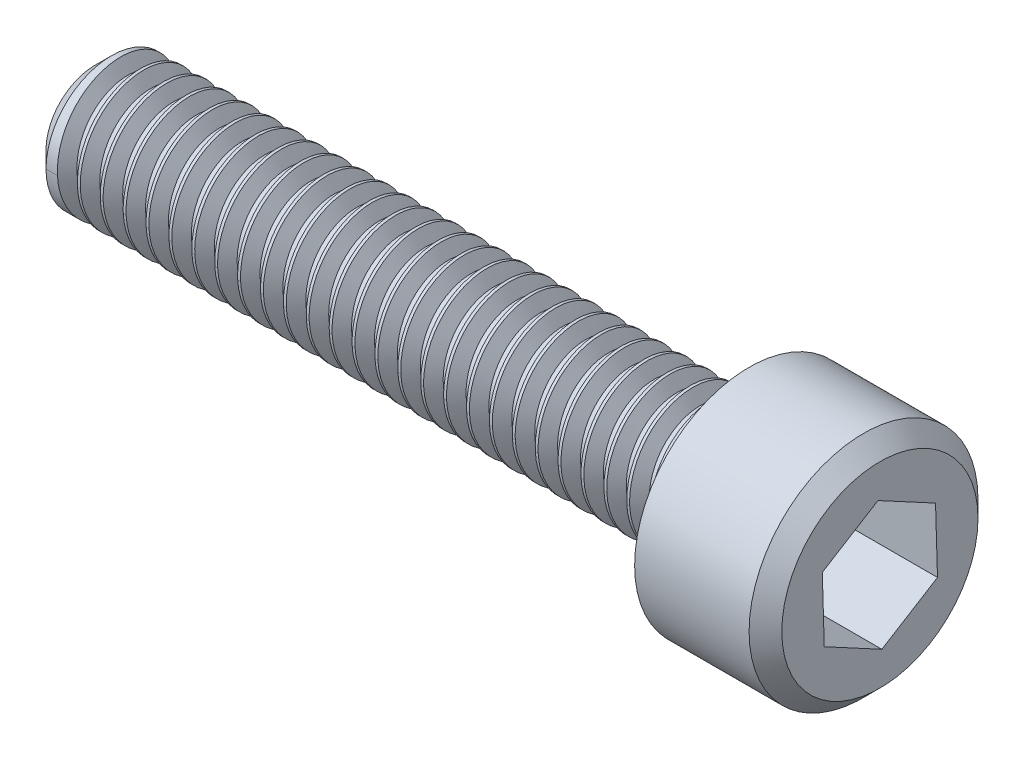
SolidWorks part; units mm, degrees
material "Хромистая нержавеющая сталь"
ref_plane "Спереди" through (0, 0, 0) normal (0, 0, 1) x (1, 0, 0)
ref_plane "Сверху" through (0, 0, 0) normal (0, 1, 0) x (1, 0, 0)
ref_plane "Справа" through (0, 0, 0) normal (1, 0, 0) x (0, 0, -1)
sketch "Эскиз1" plane through (0, 0, 0) normal (0, 0, 1) x (1, 0, 0)
  line L0 (-18.4706, 0) -> (28.3529, 0) construction
  line L1 (18.4118, 0) -> (18.4118, 3.5)
  line L2 (18.4118, 3.5) -> (14.4118, 3.5)
  line L3 (14.4118, 3.5) -> (14.4118, 2)
  line L4 (14.4118, 2) -> (-5.5882, 2)
  line L5 (-5.5882, 2) -> (-5.5882, 0)
  line L6 (-5.5882, 0) -> (18.4118, 0)
  dimension "D1" = 3.5
  dimension "D2" = 4
  dimension "D3" = 20
  dimension "D4" = 2
revolve "Повернуть1" add sketch "Эскиз1" angle 360 about L0
chamfer "Фаска1" distance 0.5 angle 45 1 edges at (-5.5882, 0, 2)
chamfer "Фаска2" distance 0.5 angle 45 1 edges at (18.4118, 0, 3.5)
sketch "Эскиз2" plane through (18.4118, 0, 0) normal (1, 0, 0) x (0, 0, -1)
  line L1 (1.7611, -0.948) -> (1.7015, 1.0511)
  line L2 (1.7015, 1.0511) -> (-0.0596, 1.9991)
  line L3 (-0.0596, 1.9991) -> (-1.7611, 0.948)
  line L4 (-1.7611, 0.948) -> (-1.7015, -1.0511)
  line L5 (-1.7015, -1.0511) -> (0.0596, -1.9991)
  line L6 (0.0596, -1.9991) -> (1.7611, -0.948)
  circle A0 centre (0, 0) radius 2 construction
extrude "Вырез-Вытянуть1" cut sketch "Эскиз2" against normal blind 3
thread "Резьба1" pitch 0.7 method cut profile "Профиль резьбы1" start angle 0, offset 0, length 18, pitch 0.7, diameter 4
ref_plane "Плоскость1" through (-5.0882, 0, -2) normal (0, -1, 0) x (0, 0, -1)
sketch "Профиль резьбы1" plane through (-5.0882, 0, -2) normal (0, -1, 0) x (0, 0, -1)
  line L0 (0, 0) -> (0, 0.7) construction
  line L11 (0, 0) -> (0, 0.6125)
  line L12 (0, 0.6125) -> (-0.3789, 0.3937)
  line L13 (-0.3789, 0.3937) -> (-0.3789, 0.2187)
  line L15 (-0.3789, 0.2187) -> (0, 0)
  line L17 (-0.3789, 0.3062) -> (0, 0.3062) construction
  point P2 (0, 0)
  dimension "Pitch" = 0.7
  dimension "Profile_Angle" = 60
  dimension "Profile_Land" = 0.175
  dimension "Profile_Height" = 0.3789
